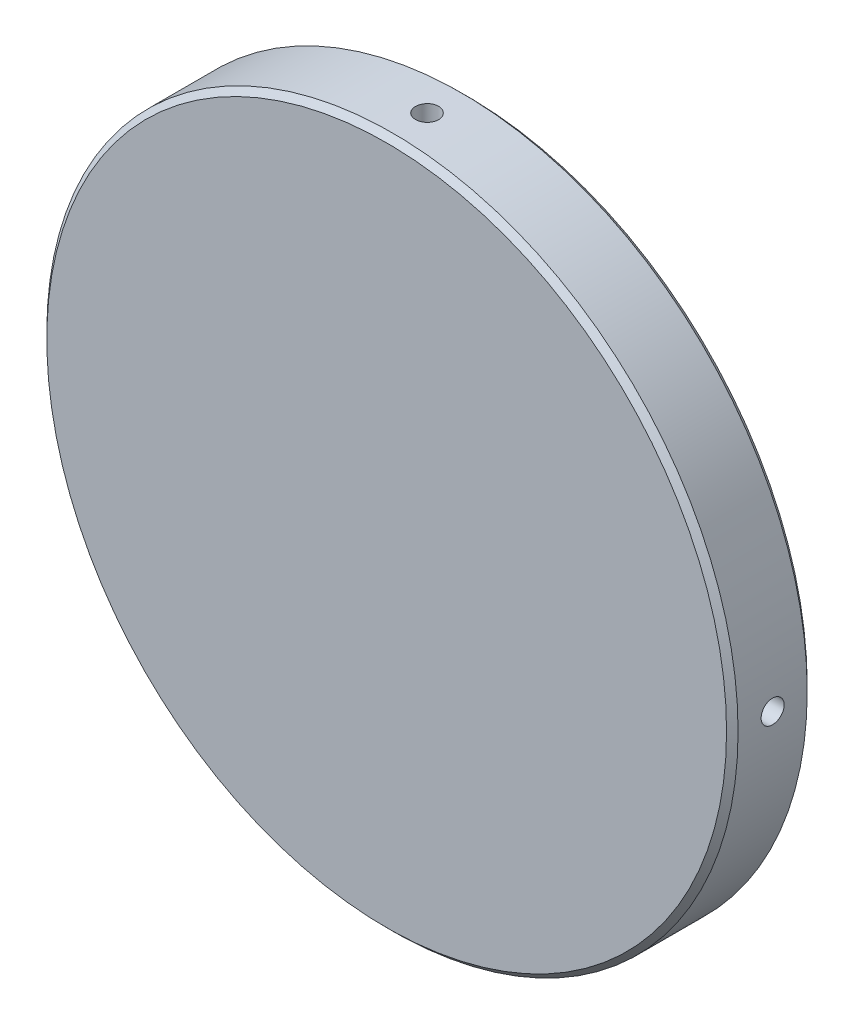
SolidWorks part; units mm, degrees
material "6063-T6"
ref_plane "Ön Düzlem" through (0, 0, 0) normal (0, 0, 1) x (1, 0, 0)
ref_plane "Üst Düzlem" through (0, 0, 0) normal (0, 1, 0) x (1, 0, 0)
ref_plane "Sağ Düzlem" through (0, 0, 0) normal (1, 0, 0) x (0, 0, -1)
sketch "Sketch1" plane through (0, 0, 0) normal (0, 0, 1) x (1, 0, 0)
  circle A0 centre (0, 0) radius 60
  dimension "D1" = 120
extrude "Boss-Extrude1" add sketch "Sketch1" along normal mid plane 14
chamfer "Chamfer1" distance 1 angle 45 2 edges at (60, 0, -7) (60, 0, 7)
sketch "Sketch2" plane through (0, 0, 0) normal (0, 1, 0) x (1, 0, 0)
  circle A0 centre (0, 0) radius 2
  dimension "D1" = 4
extrude "Cut-Extrude1" cut sketch "Sketch2" along normal blind 10 from offset 55
extrude "Cut-Extrude2" cut sketch "Sketch2<2>" against normal blind 10 from offset 55 offset against normal yes
sketch "Sketch2<2>" plane through (0, 0, 0) normal (0, 1, 0) x (1, 0, 0) same geometry as "Sketch2"
sketch "Sketch3" plane through (0, 0, 0) normal (1, 0, 0) x (0, 0, -1)
  circle A0 centre (0, 0) radius 2
extrude "Cut-Extrude3" cut sketch "Sketch3" along normal blind 10 from offset 55
extrude "Cut-Extrude4" cut sketch "Sketch3<2>" against normal blind 10 from offset 55 offset against normal yes
sketch "Sketch3<2>" plane through (0, 0, 0) normal (1, 0, 0) x (0, 0, -1) same geometry as "Sketch3"
